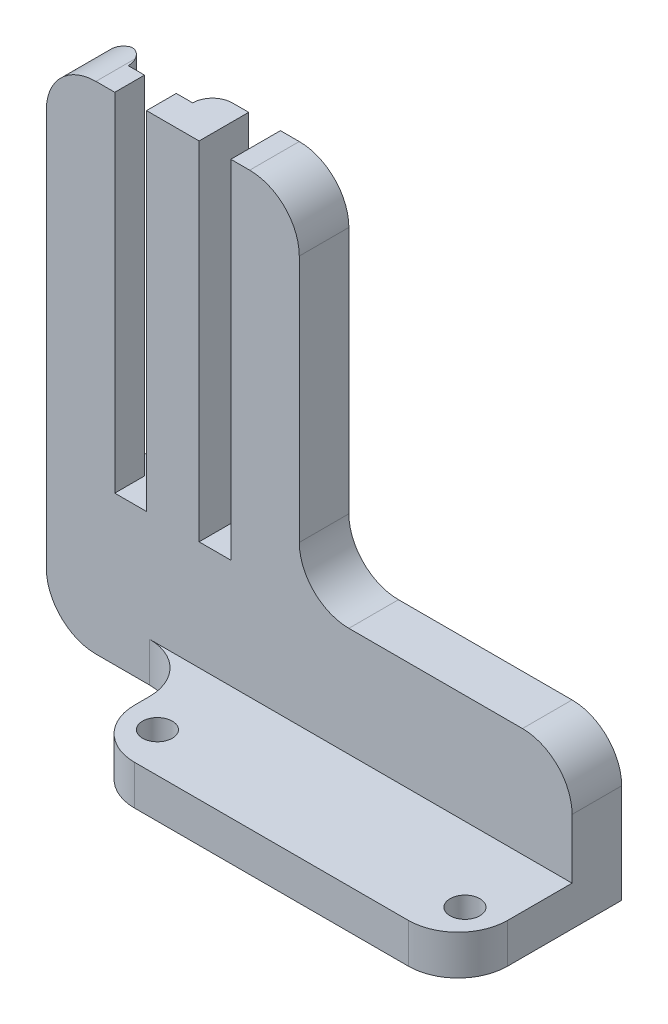
SolidWorks part; units mm, degrees
material "ABS generico"
ref_plane "Front Plane" through (0, 0, 0) normal (0, 0, 1) x (1, 0, 0)
ref_plane "Top Plane" through (0, 0, 0) normal (0, 1, 0) x (1, 0, 0)
ref_plane "Right Plane" through (0, 0, 0) normal (1, 0, 0) x (0, 0, -1)
sketch "Sketch1" plane through (0, 0, 0) normal (0, 0, 1) x (1, 0, 0)
  line L1 (26.5, -25) -> (-26.5, -25)
  line L2 (26.5, -25) -> (26.5, -10)
  line L3 (-1, 25) -> (-7.9, 25)
  line L4 (-26.5, -25) -> (-26.5, 25)
  line L5 (26.5, -25) -> (-26.5, 25) construction
  line L6 (26.5, 25) -> (-26.5, -25) construction
  line L7 (-9.5, -10) -> (-9.5, 25) construction
  line L10 (-7.9, -10) -> (-7.9, 25)
  line L11 (-11.1, -10) -> (-11.1, 25)
  line L12 (-1, -10) -> (-1, 25)
  line L13 (-19.6, 25) -> (-26.5, 25)
  line L14 (-11.1, 25) -> (-16.4, 25)
  line L15 (-1, -10) -> (26.5, -10)
  line L16 (-19.6, -10) -> (-19.6, 25)
  line L18 (-18, -10) -> (-18, 25) construction
  line L20 (-16.4, -10) -> (-16.4, 25)
  line L22 (-16.4, -10) -> (-19.6, -10)
  line L24 (-7.9, -10) -> (-11.1, -10)
  line L25 (-11.1, -25) -> (-11.1, 25) construction
  line L26 (-9.5, -25) -> (-9.5, 25) construction
  line L27 (-7.9, -25) -> (-7.9, 25) construction
  point P0 (0, 0)
  point P6 (-18, -25)
  point P10 (-16.4, -25)
  point P12 (-19.6, -25)
  point P19 (-26.5, -10)
  dimension "D1" = 53
  dimension "D2" = 50
  dimension "D7" = 1.6
  dimension "D8" = 1.6
  dimension "D9" = 8.5
extrude "Extrude1" add sketch "Sketch1" along normal blind 5
sketch "Sketch3" plane through (0, 0, 5) normal (0, 0, 1) x (1, 0, 0)
  line L0 (26.5, -10.5045) -> (26.5, -32.7354) construction
  line L1 (26.5, -25) -> (26.5, -10) construction
  line L2 (-11.1, -10) -> (-11.1, -36) construction
  line L3 (-11.1, -23) -> (26.5, -23) construction
  line L4 (7.7, -23) -> (7.7, 0) construction
  line L5 (-11.1, -25) -> (35.4785, -25) construction
  line L6 (-11.1, -21) -> (26.5, -21)
  line L7 (-11.1, -21) -> (-11.1, -25)
  line L8 (-11.1, -25) -> (26.5, -25)
  line L9 (26.5, -21) -> (26.5, -25)
  line L10 (-11.1, -21) -> (26.5, -25) construction
  line L11 (-11.1, -25) -> (26.5, -21) construction
  dimension "D1" = 2
extrude "Extrude2" add sketch "Sketch3" along normal blind 11.5
sketch "Sketch4" plane through (0, 25, 0) normal (0, 1, 0) x (1, 0, 0)
  line L0 (-16.4, 0) -> (-19.6, 0) construction
  line L1 (-21.25, -2) -> (-14.75, -2)
  line L2 (-21.25, -2) -> (-21.25, 2)
  line L3 (-21.25, 2) -> (-14.75, 2)
  line L4 (-14.75, -2) -> (-14.75, 2)
  line L5 (-21.25, -2) -> (-14.75, 2) construction
  line L6 (-21.25, 2) -> (-14.75, -2) construction
  point P0 (-18, 0)
  dimension "D1" = 6.5
  dimension "D2" = 4
sketch "Sketch5" plane through (0, -21, 0) normal (0, 1, 0) x (1, 0, 0)
  line L0 (26.5, -12.5) -> (-11.1, -12.5) construction
  line L1 (7.7, -12.5) -> (7.7, -16.5) construction
  line L2 (-11.1, -16.5) -> (26.5, -16.5) construction
  circle A0 centre (-7.8, -12.5) radius 1.5
  circle A1 centre (23.2, -12.5) radius 1.5
  dimension "D1" = 3
  dimension "D2" = 15.5
  dimension "D3" = 4
extrude "Extrude3" cut sketch "Sketch5" against normal up to surface (4 mm away) up to face at (-4.9833, -25, 8.125)
extrude "Extrude4" cut sketch "Sketch4" against normal up to surface (35 mm away) up to face at (-18, -10, 2.5)
fillet "Fillet1" radius 2 2 edges at (-14.75, 7.5, 0) (-21.25, 7.5, 0)
fillet "Fillet2" radius 5 6 edges at (26.5, -23, 16.5) (-11.1, -23, 16.5) (26.5, -10, 2.5) (-1, 25, 2.5) (-26.5, -25, 2.5) (-26.5, 25, 2.5)
fillet "Fillet3" radius 5 2 edges at (-1, -10, 2.5)
